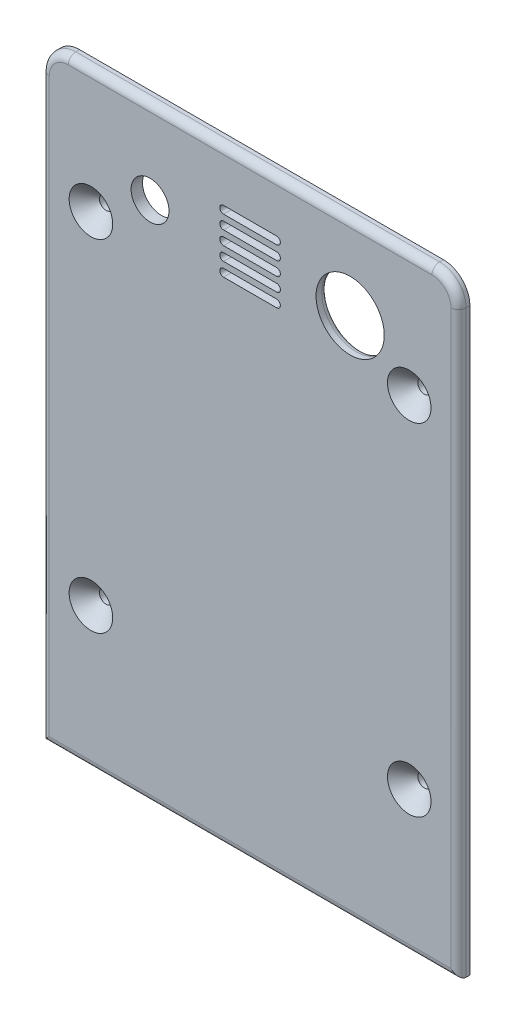
SolidWorks part; units mm, degrees
ref_plane "Front Plane" through (0, 0, 0) normal (0, 0, 1) x (1, 0, 0)
ref_plane "Top Plane" through (0, 0, 0) normal (0, 1, 0) x (1, 0, 0)
ref_plane "Right Plane" through (0, 0, 0) normal (1, 0, 0) x (0, 0, -1)
sketch "Sketch1" plane through (0, 0, 0) normal (0, 0, 1) x (1, 0, 0)
  line L1 (0, 0) -> (110, 0)
  line L2 (0, 0) -> (0, 153)
  line L3 (7, 160) -> (103, 160)
  line L4 (110, 0) -> (110, 153)
  arc A0 (103, 160) -> (110, 153) centre (103, 153) cw
  arc A1 (0, 153) -> (7, 160) centre (7, 153) cw
  point P7 (110, 160)
  point P10 (0, 160)
  dimension "D3" = 7
  dimension "D1" = 110
  dimension "D2" = 160
extrude "Boss-Extrude1" add sketch "Sketch1" along normal blind 3
fillet "Fillet1" radius 2 6 edges at (2.0503, 157.9497, 3) (55, 160, 3) (107.9497, 157.9497, 3) (110, 76.5, 3) (55, 0, 3) (0, 76.5, 3)
sketch "Sketch3" plane through (0, 0, 0) normal (0, 0, -1) x (-1, 0, 0)
  line L0 (0, 0) -> (-110, 0) construction
  line L1 (-103, 0) -> (-7, 0)
  line L2 (-103, 0) -> (-103, 152.5)
  line L3 (-103, 152.5) -> (-7, 152.5)
  line L4 (-7, 0) -> (-7, 152.5)
  line L5 (-101.4, 1.6) -> (-101.4, 33.5)
  line L6 (-101.4, 150.9) -> (-8.6, 150.9)
  line L7 (-8.6, 1.6) -> (-8.6, 33.5)
  line L8 (-101.4, 1.6) -> (-8.6, 1.6)
  line L9 (-97, 131.5) -> (-101.4, 131.5)
  line L10 (-97, 123.5) -> (-101.4, 123.5)
  line L11 (-13, 131.5) -> (-8.6, 131.5)
  line L12 (-8.6, 123.5) -> (-13, 123.5)
  line L13 (-13, 33.5) -> (-8.6, 33.5)
  line L14 (-13, 41.5) -> (-8.6, 41.5)
  line L15 (-97, 41.5) -> (-101.4, 41.5)
  line L16 (-101.4, 33.5) -> (-97, 33.5)
  line L17 (-101.4, 41.5) -> (-101.4, 123.5)
  line L18 (-8.6, 41.5) -> (-8.6, 123.5)
  line L19 (-101.4, 1.6) -> (-101.4, 150.9) construction
  line L20 (-8.6, 131.5) -> (-8.6, 150.9)
  line L21 (-8.6, 1.6) -> (-8.6, 150.9) construction
  line L22 (-101.4, 131.5) -> (-101.4, 150.9)
  arc A0 (-97, 123.5) -> (-97, 131.5) centre (-97, 127.5) ccw
  arc A1 (-13, 131.5) -> (-13, 123.5) centre (-13, 127.5) ccw
  arc A2 (-97, 33.5) -> (-97, 41.5) centre (-97, 37.5) ccw
  arc A3 (-13, 41.5) -> (-13, 33.5) centre (-13, 37.5) ccw
  point P6 (-55, 0)
  point P7 (-55, 0)
  dimension "D4" = 8
  dimension "D5" = 6
  dimension "D6" = 6
  dimension "D8" = 90
  dimension "D1" = 96
  dimension "D2" = 152.5
  dimension "D7" = 25
  dimension "D3" = 1.6
extrude "Boss-Extrude2" add sketch "Sketch3" along normal blind 3.9
sketch "Sketch4" plane through (0, 0, -3.9) normal (0, 0, -1) x (-1, 0, 0)
  circle A0 centre (-97, 127.5) radius 1.75
  circle A1 centre (-13, 127.5) radius 1.75
  circle A2 centre (-13, 37.5) radius 1.75
  circle A3 centre (-97, 37.5) radius 1.75
  dimension "D1" = 3.5
extrude "Cut-Extrude1" cut sketch "Sketch4" against normal up to next
chamfer "Chamfer1" distance 4 angle 45 4 edges at (95.25, 37.5, 3) (11.25, 37.5, 3) (11.25, 127.5, 3) (95.25, 127.5, 3)
sketch "Sketch5" plane through (0, 0, 0) normal (0, 0, -1) x (-1, 0, 0)
  line L0 (-8.6, 150.9) -> (-101.4, 150.9) construction
  line L1 (-8.6, 131.5) -> (-8.6, 150.9) construction
  line L2 (-101.4, 150.9) -> (-101.4, 131.5) construction
  circle A0 centre (-28.6, 137.9) radius 5
  circle A1 centre (-81.4, 137.9) radius 9
  point P8 (0, 0)
  dimension "D1" = 13
  dimension "D2" = 20
  dimension "D3" = 10
  dimension "D4" = 18
  dimension "D5" = 20
extrude "Cut-Extrude2" cut sketch "Sketch5" against normal through all
fillet "Fillet2" radius 1.5 1 edges at (72.4, 137.9, 0)
sketch "Sketch7" plane through (0, 0, 0) normal (0, 0, -1) x (-1, 0, 0)
  line L0 (-8.6, 150.9) -> (-101.4, 150.9) construction
  line L1 (-65, 147.9) -> (-45, 147.9)
  line L2 (-65, 147.9) -> (-65, 127.9)
  line L3 (-65, 127.9) -> (-45, 127.9)
  line L4 (-45, 147.9) -> (-45, 127.9)
  line L5 (-64, 146.9) -> (-46, 146.9)
  line L6 (-46, 146.9) -> (-46, 128.9)
  line L7 (-64, 128.9) -> (-46, 128.9)
  line L8 (-64, 146.9) -> (-64, 128.9)
  point P6 (-55, 150.9)
  point P7 (-55, 147.9)
  dimension "D1" = 20
  dimension "D2" = 20
  dimension "D3" = 3
  dimension "D4" = 1
extrude "Boss-Extrude3" add sketch "Sketch7" along normal up to surface (3.9 mm away) up to face at (95.25, 37.5, -3.9)
sketch "Sketch8" plane through (0, 0, 0) normal (0, 0, -1) x (-1, 0, 0)
  line L0 (-62, 145.4) -> (-48, 145.4) construction
  line L1 (-62, 146.4) -> (-48, 146.4)
  line L2 (-62, 144.4) -> (-48, 144.4)
  line L3 (-46, 146.9) -> (-64, 146.9) construction
  line L4 (-62, 141.8) -> (-48, 141.8) construction
  line L5 (-62, 142.8) -> (-48, 142.8)
  line L6 (-62, 140.8) -> (-48, 140.8)
  line L7 (-62, 138.2) -> (-48, 138.2) construction
  line L8 (-62, 139.2) -> (-48, 139.2)
  line L9 (-62, 137.2) -> (-48, 137.2)
  line L10 (-62, 134.6) -> (-48, 134.6) construction
  line L11 (-62, 135.6) -> (-48, 135.6)
  line L12 (-62, 133.6) -> (-48, 133.6)
  line L13 (-62, 131) -> (-48, 131) construction
  line L14 (-62, 132) -> (-48, 132)
  line L15 (-62, 130) -> (-48, 130)
  arc A0 (-62, 146.4) -> (-62, 144.4) centre (-62, 145.4) ccw
  arc A1 (-48, 144.4) -> (-48, 146.4) centre (-48, 145.4) ccw
  arc A2 (-62, 142.8) -> (-62, 140.8) centre (-62, 141.8) ccw
  arc A3 (-48, 140.8) -> (-48, 142.8) centre (-48, 141.8) ccw
  arc A4 (-62, 139.2) -> (-62, 137.2) centre (-62, 138.2) ccw
  arc A5 (-48, 137.2) -> (-48, 139.2) centre (-48, 138.2) ccw
  arc A6 (-62, 135.6) -> (-62, 133.6) centre (-62, 134.6) ccw
  arc A7 (-48, 133.6) -> (-48, 135.6) centre (-48, 134.6) ccw
  arc A8 (-62, 132) -> (-62, 130) centre (-62, 131) ccw
  arc A9 (-48, 130) -> (-48, 132) centre (-48, 131) ccw
  point P2 (-55, 145.4)
  point P9 (-55, 146.9)
  point P14 (-55, 141.8)
  point P21 (-55, 138.2)
  point P28 (-55, 134.6)
  point P35 (-55, 131)
  dimension "D2" = 1
  dimension "D1" = 14
  dimension "D3" = 1.5
  dimension "D4" = 5
extrude "Cut-Extrude3" cut sketch "Sketch8" against normal through all
